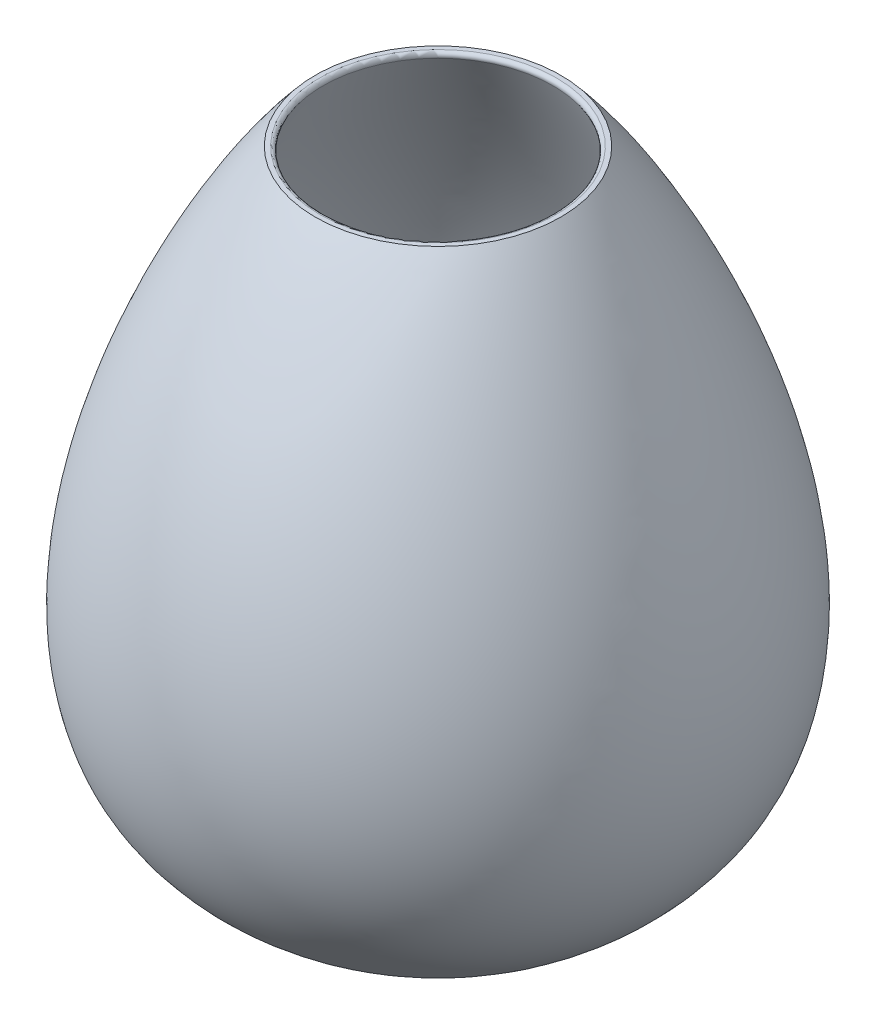
SolidWorks part; units mm, degrees
ref_plane "前视基准面" through (0, 0, 0) normal (0, 0, 1) x (1, 0, 0)
ref_plane "上视基准面" through (0, 0, 0) normal (0, 1, 0) x (1, 0, 0)
ref_plane "右视基准面" through (0, 0, 0) normal (1, 0, 0) x (0, 0, -1)
sketch "草图1" plane through (0, 0, 0) normal (0, 0, 1) x (1, 0, 0)
  line L0 (0, 116.4331) -> (0, -105.6658) construction
  line L1 (16.9963, 90) -> (0, 90)
  line L2 (0, 90) -> (0, 0)
  spline S0 degree 3 poles (0, 0) (12.4029, -0.1686) (56.4588, 19.3983) (28.1208, 77.1435) (16.9963, 90) knots 0 0 0 0 0.33276 1 1 1 1
  spline S1 degree 3 poles (15.5467, 90) (21.4224, 78.7522) (30.9821, 60.2072) (32.6434, 23.7289) (9.986, 13.9821) (0, 14.6276) knots 0 0 0 0 0.389146 0.673137 1 1 1 1
  dimension "D1" = 90
revolve "旋转1" [suppressed] add sketch "草图1" angle 360 about L0
revolve "旋转2" add sketch "草图1<2>" angle 360 about L0 region at (37.3, 35.9372, 0)
sketch "草图1<2>" plane through (0, 0, 0) normal (0, 0, 1) x (1, 0, 0) same geometry as "草图1"
fillet "圆角1" radius 0.5 1 edges at (0, 90, 15.5467)
